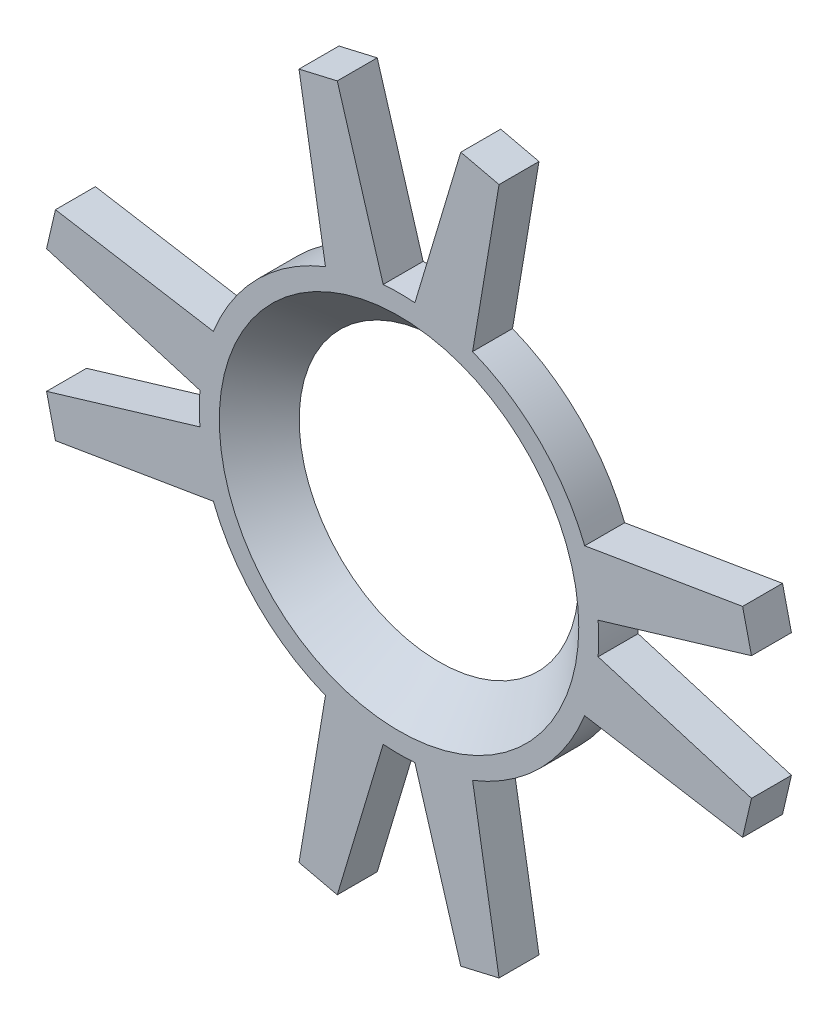
SolidWorks part; units mm, degrees
material "PMMA"
ref_plane "Front Plane" through (0, 0, 0) normal (0, 0, 1) x (1, 0, 0)
ref_plane "Top Plane" through (0, 0, 0) normal (0, 1, 0) x (1, 0, 0)
ref_plane "Right Plane" through (0, 0, 0) normal (1, 0, 0) x (0, 0, -1)
sketch "草图1" plane through (0, 0, 0) normal (0, 0, 1) x (1, 0, 0)
  circle A0 centre (0, 0) radius 20
extrude "凸台-拉伸1" add sketch "草图1" along normal blind 2
sketch "草图2" plane through (0, 0, 2) normal (0, 0, 1) x (1, 0, 0)
  circle A0 centre (0, 0) radius 7
extrude "切除-拉伸1" cut sketch "草图2" against normal blind 2
sketch "草图3" plane through (0, 0, 2) normal (0, 0, 1) x (1, 0, 0)
  line L0 (0, 0) -> (-4.5277, 19.4808) construction
  line L1 (0, 22.2151) -> (0, -23.7941) construction
  line L2 (17.2023, 5.0077) -> (9.2968, 3.6837)
  line L3 (-4.5277, 19.4808) -> (-4.0498, 17.4249) construction
  line L4 (-5.0077, 17.2023) -> (-3.092, 17.6476)
  line L5 (-5.0077, 17.2023) -> (-3.6837, 9.2968)
  line L6 (17.2023, 5.0077) -> (17.6476, 3.092)
  line L7 (-3.092, 17.6476) -> (-0.7939, 9.9684)
  line L8 (17.6476, 3.092) -> (9.9684, 0.7939)
  line L9 (3.092, 17.6476) -> (0.7939, 9.9684)
  line L10 (17.6476, -3.092) -> (9.9684, -0.7939)
  line L11 (5.0077, 17.2023) -> (3.6837, 9.2968)
  line L12 (5.0077, 17.2023) -> (3.092, 17.6476)
  line L13 (17.2023, -5.0077) -> (17.6476, -3.092)
  line L14 (17.2023, -5.0077) -> (9.2968, -3.6837)
  line L15 (5.0077, -17.2023) -> (3.6837, -9.2968)
  line L16 (5.0077, -17.2023) -> (3.092, -17.6476)
  line L17 (3.092, -17.6476) -> (0.7939, -9.9684)
  line L18 (-3.092, -17.6476) -> (-0.7939, -9.9684)
  line L19 (-5.0077, -17.2023) -> (-3.092, -17.6476)
  line L20 (-5.0077, -17.2023) -> (-3.6837, -9.2968)
  line L21 (-17.2023, -5.0077) -> (-9.2968, -3.6837)
  line L22 (-17.2023, -5.0077) -> (-17.6476, -3.092)
  line L23 (-17.6476, -3.092) -> (-9.9684, -0.7939)
  line L24 (-17.6476, 3.092) -> (-9.9684, 0.7939)
  line L25 (-17.2023, 5.0077) -> (-17.6476, 3.092)
  line L26 (-17.2023, 5.0077) -> (-9.2968, 3.6837)
  circle A0 centre (0, 0) radius 9
  circle A1 centre (0, 0) radius 10
  circle A2 centre (0, 0) radius 20 construction
  point P12 (-2.2638, 9.7404)
  point P47 (0, 0)
  dimension "D1" = 4
extrude "切除-拉伸2" cut sketch "草图3" against normal blind 2 flip side to cut contours A1 L7 L4 L5 | A1 L26 L25 L24 | A1 L23 L22 L21 | A1 L8 L6 L2 | A1 L11 L12 L9 | A1 L17 L16 L15 | A1 L20 L19 L18 | A1 L14 L13 L10 | A1 region at (13.3058, 3.0925, 2) region at (3.0925, 13.3058, 2) region at (13.3058, -3.0925, 2) region at (-3.0925, 13.3058, 2) region at (3.0925, -13.3058, 2) region at (-13.3058, 3.0925, 2) region at (-3.0925, -13.3058, 2) region at (-13.3058, -3.0925, 2)
chamfer "倒角4" distance 2 angle 45 1 edges at (7, 0, 2)
